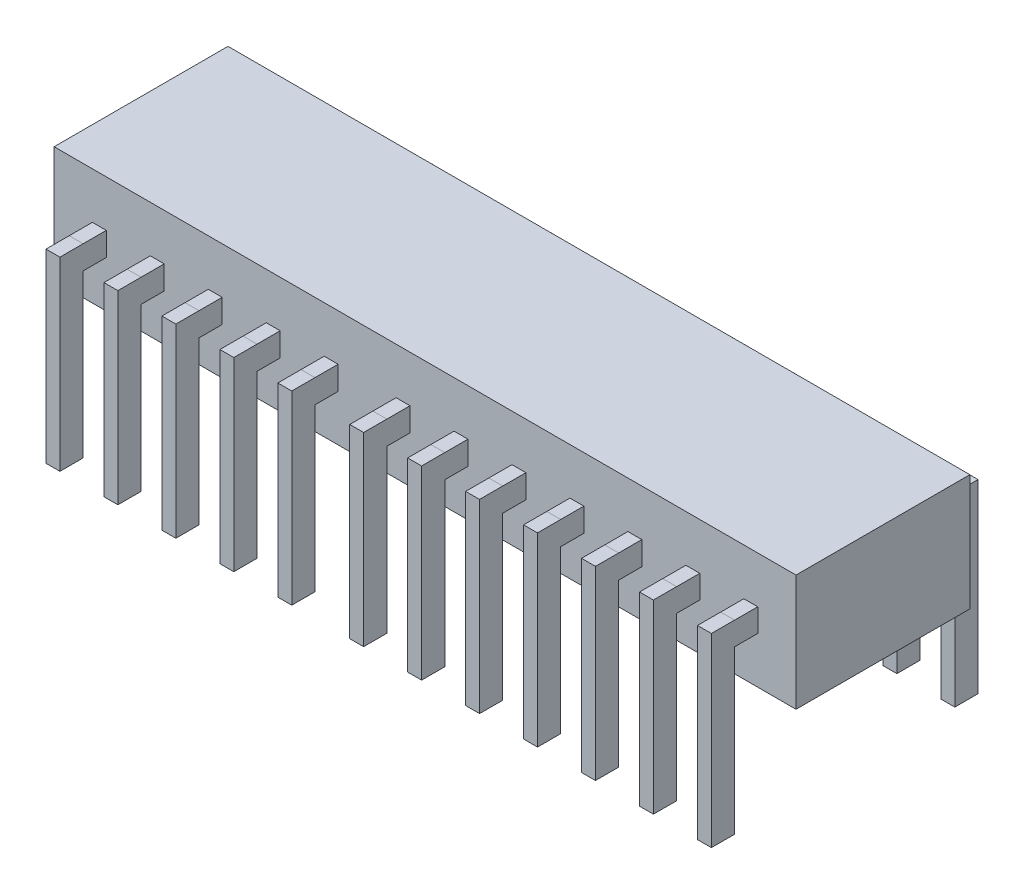
SolidWorks part; units mm, degrees
ref_plane "Front Plane" through (0, 0, 0) normal (0, 0, 1) x (1, 0, 0)
ref_plane "Top Plane" through (0, 0, 0) normal (0, 1, 0) x (1, 0, 0)
ref_plane "Right Plane" through (0, 0, 0) normal (1, 0, 0) x (0, 0, -1)
sketch "Sketch1" plane through (0, 0, 0) normal (0, 1, 0) x (1, 0, 0)
  line L0 (-13500, -3750) -> (18500.0025, -3750)
  line L1 (-13500, -3750) -> (-13500, 3750)
  line L2 (-13500, 3750) -> (18500.0025, 3750)
  line L3 (18500.0025, 3750) -> (18500.0025, -3750)
  line L4 (-11250, 5750) -> (-11850, 5750)
  line L5 (11850, -4750) -> (11850, -5750)
  line L6 (11850, -4750) -> (11250, -4750)
  line L7 (1250, -5750) -> (1250, -3750)
  line L8 (1250, -5750) -> (1850, -5750)
  line L9 (1850, -5750) -> (1850, -3750)
  line L10 (3750, -5750) -> (4350, -5750)
  line L11 (3750, -5750) -> (3750, -3750)
  line L12 (6250, -5750) -> (6850, -5750)
  line L13 (4350, -5750) -> (4350, -3750)
  line L14 (8750, -5750) -> (9350, -5750)
  line L15 (6250, -5750) -> (6250, -3750)
  line L16 (11250, -5750) -> (11850, -5750)
  line L17 (6850, -5750) -> (6850, -3750)
  line L18 (8750, -5750) -> (8750, -3750)
  line L19 (9350, -5750) -> (9350, -3750)
  line L20 (-11850, -5750) -> (-11850, -3750)
  line L21 (-11250, -5750) -> (-11250, -3750)
  line L22 (-9350, -5750) -> (-9350, -3750)
  line L23 (-8750, -5750) -> (-8750, -3750)
  line L24 (-6850, -5750) -> (-6850, -3750)
  line L25 (-11250, -5750) -> (-11850, -5750)
  line L26 (-6250, -5750) -> (-6250, -3750)
  line L27 (-8750, -5750) -> (-9350, -5750)
  line L28 (-4350, -5750) -> (-4350, -3750)
  line L29 (-6250, -5750) -> (-6850, -5750)
  line L30 (-3750, -5750) -> (-3750, -3750)
  line L31 (-3750, -5750) -> (-4350, -5750)
  line L32 (-1850, -5750) -> (-1850, -3750)
  line L33 (-1250, -5750) -> (-1850, -5750)
  line L34 (-1250, -5750) -> (-1250, -3750)
  line L35 (11250, -5750) -> (11250, -3750)
  line L36 (-1250, 5750) -> (-1250, 3750)
  line L37 (-1250, 5750) -> (-1850, 5750)
  line L38 (-1850, 5750) -> (-1850, 3750)
  line L39 (-3750, 5750) -> (-4350, 5750)
  line L40 (-3750, 5750) -> (-3750, 3750)
  line L41 (-6250, 5750) -> (-6850, 5750)
  line L42 (-4350, 5750) -> (-4350, 3750)
  line L43 (-8750, 5750) -> (-9350, 5750)
  line L44 (-6250, 5750) -> (-6250, 3750)
  line L45 (11850, -5750) -> (11850, -3750)
  line L46 (-6850, 5750) -> (-6850, 3750)
  line L47 (-8750, 5750) -> (-8750, 3750)
  line L48 (-9350, 5750) -> (-9350, 3750)
  line L49 (-11250, 5750) -> (-11250, 3750)
  line L50 (-11850, 5750) -> (-11850, 3750)
  line L51 (11850, 5750) -> (11850, 3750)
  line L52 (11250, 5750) -> (11250, 3750)
  line L53 (9350, 5750) -> (9350, 3750)
  line L54 (8750, 5750) -> (8750, 3750)
  line L55 (6850, 5750) -> (6850, 3750)
  line L56 (11250, 5750) -> (11850, 5750)
  line L57 (6250, 5750) -> (6250, 3750)
  line L58 (8750, 5750) -> (9350, 5750)
  line L59 (4350, 5750) -> (4350, 3750)
  line L60 (6250, 5750) -> (6850, 5750)
  line L61 (3750, 5750) -> (3750, 3750)
  line L62 (3750, 5750) -> (4350, 5750)
  line L63 (1850, 5750) -> (1850, 3750)
  line L64 (1250, 5750) -> (1850, 5750)
  line L65 (1250, 5750) -> (1250, 3750)
  line L66 (11250, -5750) -> (11250, -4750)
  line L67 (16850, -3750) -> (18500, -3750)
  line L68 (9350, -4750) -> (9350, -5750)
  line L69 (9350, -4750) -> (8750, -4750)
  line L70 (8750, -5750) -> (9350, -5750)
  line L71 (8750, -5750) -> (8750, -4750)
  line L72 (6850, -4750) -> (6850, -5750)
  line L73 (6850, -4750) -> (6250, -4750)
  line L74 (6250, -5750) -> (6850, -5750)
  line L75 (6250, -5750) -> (6250, -4750)
  line L76 (1850, -4750) -> (1850, -5750)
  line L77 (1850, -4750) -> (1250, -4750)
  line L78 (1250, -5750) -> (1850, -5750)
  line L79 (1250, -5750) -> (1250, -4750)
  line L80 (4350, -4750) -> (4350, -5750)
  line L81 (4350, -4750) -> (3750, -4750)
  line L82 (3750, -5750) -> (4350, -5750)
  line L83 (3750, -5750) -> (3750, -4750)
  line L84 (-1250, -4750) -> (-1250, -5750)
  line L85 (-1250, -4750) -> (-1850, -4750)
  line L86 (-11850, -5750) -> (-11250, -5750)
  line L87 (-9350, -5750) -> (-8750, -5750)
  line L88 (-6850, -5750) -> (-6250, -5750)
  line L89 (-4350, -5750) -> (-3750, -5750)
  line L90 (-1850, -5750) -> (-1250, -5750)
  line L91 (-1850, -5750) -> (-1850, -4750)
  line L92 (-3750, -4750) -> (-3750, -5750)
  line L93 (-3750, -4750) -> (-4350, -4750)
  line L94 (-4350, -5750) -> (-3750, -5750)
  line L95 (-4350, -5750) -> (-4350, -4750)
  line L96 (-6250, -4750) -> (-6250, -5750)
  line L97 (-6250, -4750) -> (-6850, -4750)
  line L98 (-6850, -5750) -> (-6250, -5750)
  line L99 (-6850, -5750) -> (-6850, -4750)
  line L100 (-11250, -4750) -> (-11250, -5750)
  line L101 (-11250, -4750) -> (-11850, -4750)
  line L102 (-11850, -5750) -> (-11250, -5750)
  line L103 (-11850, -5750) -> (-11850, -4750)
  line L104 (-8750, -4750) -> (-8750, -5750)
  line L105 (-8750, -4750) -> (-9350, -4750)
  line L106 (-9350, -5750) -> (-8750, -5750)
  line L107 (-9350, -5750) -> (-9350, -4750)
  line L108 (11850, 5750) -> (11850, 4750)
  line L109 (11850, 5750) -> (11250, 5750)
  line L110 (1250, 4750) -> (1850, 4750)
  line L111 (3750, 4750) -> (4350, 4750)
  line L112 (6250, 4750) -> (6850, 4750)
  line L113 (8750, 4750) -> (9350, 4750)
  line L114 (11250, 4750) -> (11850, 4750)
  line L115 (11250, 4750) -> (11250, 5750)
  line L116 (9350, 5750) -> (9350, 4750)
  line L117 (9350, 5750) -> (8750, 5750)
  line L118 (8750, 4750) -> (9350, 4750)
  line L119 (8750, 4750) -> (8750, 5750)
  line L120 (6850, 5750) -> (6850, 4750)
  line L121 (6850, 5750) -> (6250, 5750)
  line L122 (6250, 4750) -> (6850, 4750)
  line L123 (6250, 4750) -> (6250, 5750)
  line L124 (1850, 5750) -> (1850, 4750)
  line L125 (1850, 5750) -> (1250, 5750)
  line L126 (1250, 4750) -> (1850, 4750)
  line L127 (1250, 4750) -> (1250, 5750)
  line L128 (4350, 5750) -> (4350, 4750)
  line L129 (4350, 5750) -> (3750, 5750)
  line L130 (3750, 4750) -> (4350, 4750)
  line L131 (3750, 4750) -> (3750, 5750)
  line L132 (-1250, 5750) -> (-1250, 4750)
  line L133 (-1250, 5750) -> (-1850, 5750)
  line L134 (-11850, 4750) -> (-11250, 4750)
  line L135 (-9350, 4750) -> (-8750, 4750)
  line L136 (-6850, 4750) -> (-6250, 4750)
  line L137 (-4350, 4750) -> (-3750, 4750)
  line L138 (-1850, 4750) -> (-1250, 4750)
  line L139 (-1850, 4750) -> (-1850, 5750)
  line L140 (-3750, 5750) -> (-3750, 4750)
  line L141 (-3750, 5750) -> (-4350, 5750)
  line L142 (-4350, 4750) -> (-3750, 4750)
  line L143 (-4350, 4750) -> (-4350, 5750)
  line L144 (-6250, 5750) -> (-6250, 4750)
  line L145 (-6250, 5750) -> (-6850, 5750)
  line L146 (-6850, 4750) -> (-6250, 4750)
  line L147 (-6850, 4750) -> (-6850, 5750)
  line L148 (-11250, 5750) -> (-11250, 4750)
  line L149 (-11250, 5750) -> (-11850, 5750)
  line L150 (-11850, 4750) -> (-11250, 4750)
  line L151 (-11850, 4750) -> (-11850, 5750)
  line L152 (-8750, 5750) -> (-8750, 4750)
  line L153 (-8750, 5750) -> (-9350, 5750)
  line L154 (-9350, 4750) -> (-8750, 4750)
  line L155 (-9350, 4750) -> (-9350, 5750)
  line L156 (13750, -5750) -> (14350, -5750)
  line L157 (16250, -5750) -> (16850, -5750)
  line L158 (13750, -5750) -> (13750, -3750)
  line L159 (14350, -5750) -> (14350, -3750)
  line L160 (16250, -5750) -> (16250, -3750)
  line L161 (16850, -5750) -> (16850, -3750)
  line L162 (16850, -4750) -> (16850, -5750)
  line L163 (16850, -4750) -> (16250, -4750)
  line L164 (16250, -5750) -> (16850, -5750)
  line L165 (16250, -5750) -> (16250, -4750)
  line L166 (14350, -4750) -> (14350, -5750)
  line L167 (14350, -4750) -> (13750, -4750)
  line L168 (13750, -5750) -> (14350, -5750)
  line L169 (13750, -5750) -> (13750, -4750)
  line L171 (13750, 5750) -> (13750, 4750)
  line L172 (13750, 5750) -> (14350, 5750)
  line L173 (14350, 4750) -> (13750, 4750)
  line L174 (14350, 4750) -> (14350, 5750)
  line L175 (16250, 5750) -> (16250, 4750)
  line L176 (16250, 5750) -> (16850, 5750)
  line L177 (16850, 4750) -> (16250, 4750)
  line L178 (16850, 4750) -> (16850, 5750)
  line L179 (16850, 5750) -> (16850, 3750)
  line L180 (16250, 5750) -> (16250, 3750)
  line L181 (14350, 5750) -> (14350, 3750)
  line L182 (13750, 5750) -> (13750, 3750)
  line L183 (16250, 5750) -> (16850, 5750)
  line L184 (13750, 5750) -> (14350, 5750)
sketch "Sketch2" plane through (0, 0, 0) normal (0, 0, 1) x (1, 0, 0)
  line L0 (1250, 500) -> (1250, -7500)
  line L1 (-9350, 500) -> (-8750, 500)
  line L2 (1250, -7500) -> (1850, -7500)
  line L3 (1850, -7500) -> (1850, 500)
  line L4 (-11850.0182, 500) -> (-11250, 500)
  line L5 (3750, 500) -> (3750, -7500)
  line L6 (-6850, 500) -> (-6250, 500)
  line L7 (-4350, 500) -> (-3750, 500)
  line L8 (3750, -7500) -> (4350, -7500)
  line L9 (4350, -7500) -> (4350, 500)
  line L10 (-1850, 500) -> (-1250, 500)
  line L11 (6250, 500) -> (6250, -7500)
  line L12 (1250, 500) -> (1850, 500)
  line L13 (6250, -7500) -> (6850, -7500)
  line L14 (6850, -7500) -> (6850, 500)
  line L15 (8750, 500) -> (8750, -7500)
  line L16 (3750, 500) -> (4350, 500)
  line L17 (8750, -7500) -> (9350, -7500)
  line L18 (9350, -7500) -> (9350, 500)
  line L19 (11250, 500) -> (11250, -7500)
  line L20 (6250, 500) -> (6850, 500)
  line L21 (11250, -7500) -> (11850, -7500)
  line L22 (11850, -7500) -> (11850, 500)
  line L24 (-13553.4759, -2500) -> (13446.5241, -2500)
  line L25 (-11850.0182, -7500) -> (-11850.0182, 500)
  line L26 (-11250, -7500) -> (-11850.0182, -7500)
  line L27 (-11250, 500) -> (-11250, -7500)
  line L28 (-9350, -7500) -> (-9350, 500)
  line L29 (-8750, -7500) -> (-9350, -7500)
  line L30 (-8750, 500) -> (-8750, -7500)
  line L31 (-6850, -7500) -> (-6850, 500)
  line L32 (-6250, -7500) -> (-6850, -7500)
  line L33 (-6250, 500) -> (-6250, -7500)
  line L34 (-4350, -7500) -> (-4350, 500)
  line L35 (-3750, -7500) -> (-4350, -7500)
  line L36 (-3750, 500) -> (-3750, -7500)
  line L37 (-1850, -7500) -> (-1850, 500)
  line L38 (-1250, -7500) -> (-1850, -7500)
  line L39 (-1250, 500) -> (-1250, -7500)
  line L40 (13446.5241, -2500) -> (13446.5241, 2500)
  line L41 (8750, 500) -> (9350, 500)
  line L45 (13446.5241, 2500) -> (-13553.4759, 2500)
  line L46 (-13553.4759, 2500) -> (-13553.4759, -2500)
  line L47 (11250, 500) -> (11850, 500)
sketch "Sketch3" plane through (0, 0, 0) normal (1, 0, 0) x (0, 0, -1)
  line L1 (3750, 2500) -> (-3750, 2500)
  line L6 (3750, 500) -> (5750, 500)
  line L7 (5750, 500) -> (5750, -7500)
  line L8 (5750, -7500) -> (4750, -7500)
  line L9 (-3750, 2500) -> (-3750, -2500)
  line L10 (-3750, -2500) -> (3750, -2500)
  line L11 (3750, -2500) -> (3750, 2500)
  line L12 (4750, -7500) -> (4750, -500)
  line L13 (4750, -500) -> (3750, -500)
  line L15 (-4750, -500) -> (-3750, -500)
  line L16 (-4750, -7500) -> (-4750, -500)
  line L17 (-5750, -7500) -> (-4750, -7500)
  line L18 (-5750, 500) -> (-5750, -7500)
  line L19 (-3750, 500) -> (-5750, 500)
extrude "Boss-Extrude3" add sketch "Sketch1" along normal mid plane 5015 contours L3 L2 L1 L0 region at (2500.0013, 0, 0)
extrude "Boss-Extrude6" add sketch "Sketch1<14>" against normal blind 7494 and the other way blind 508 separate body contours L35 L16 L5 L6 | L19 L69 L18 L14 | L17 L73 L15 L12 | L13 L81 L11 L10 | L9 L77 L7 L8 | L34 L85 L32 L33 | L30 L93 L28 L31 | L26 L97 L24 L29 | L23 L105 L22 L27 | L21 L101 L20 L25 | L50 L134 L49 L4 | L48 L135 L47 L43 | L46 L136 L44 L41 | L42 L137 L40 L39 | L38 L138 L36 L37 | L65 L110 L63 L64 | L61 L111 L59 L62 | L57 L112 L55 L60 | L54 L113 L53 L58 | L52 L114 L51 L56 region at (-11550, 0, 5250) region at (-11550, 0, -5250) region at (-9050, 0, 5250) region at (-9050, 0, -5250) region at (-6550, 0, 5250) region at (-6550, 0, -5250) region at (-4050, 0, 5250) region at (-4050, 0, -5250) region at (-1550, 0, 5250) region at (-1550, 0, -5250) region at (1550, 0, 5250) region at (1550, 0, -5250) region at (4050, 0, 5250) region at (4050, 0, -5250) region at (6550, 0, 5250) region at (6550, 0, -5250) region at (9050, 0, 5250) region at (9050, 0, -5250) region at (11550, 0, 5250) region at (11550, 0, -5250)
sketch "Sketch1<14>" plane through (0, 0, 0) normal (0, 1, 0) x (1, 0, 0) same geometry as "Sketch1"
extrude "Boss-Extrude8" add sketch "Sketch1<17>" along normal mid plane 1015 contours L6 L45 L0 L35 | L69 L19 L0 L18 | L114 L52 L2 L51 | L113 L54 L2 L53 | L112 L57 L2 L55 | L73 L17 L0 L15 | L81 L13 L0 L11 | L77 L9 L0 L7 | L85 L34 L0 L32 | L138 L38 L2 L36 | L110 L65 L2 L63 | L111 L61 L2 L59 | L93 L30 L0 L28 | L97 L26 L0 L24 | L137 L42 L2 L40 | L136 L46 L2 L44 | L135 L48 L2 L47 | L105 L23 L0 L22 | L101 L21 L0 L20 | L134 L50 L2 L49 region at (-11550, 0, 4250) region at (-11550, 0, -4250) region at (-9050, 0, 4250) region at (-9050, 0, -4250) region at (-6550, 0, 4250) region at (-6550, 0, -4250) region at (-4050, 0, 4250) region at (-4050, 0, -4250) region at (-1550, 0, 4250) region at (-1550, 0, -4250) region at (1550, 0, 4250) region at (1550, 0, -4250) region at (4050, 0, 4250) region at (4050, 0, -4250) region at (6550, 0, 4250) region at (6550, 0, -4250) region at (9050, 0, 4250) region at (9050, 0, -4250) region at (11550, 0, 4250) region at (11550, 0, -4250)
sketch "Sketch1<17>" plane through (0, 0, 0) normal (0, 1, 0) x (1, 0, 0) same geometry as "Sketch1"
extrude "Boss-Extrude9" add sketch "Sketch1<18>" against normal blind 7501 and the other way blind 500 separate body contours L159 L167 L158 L156 | L161 L163 L160 L157 | L173 L174 L172 L171 | L177 L178 L176 L175 region at (14050, 0, 5250) region at (14050, 0, -5250) region at (16550, 0, 5250) region at (16550, 0, -5250)
sketch "Sketch1<18>" plane through (0, 0, 0) normal (0, 1, 0) x (1, 0, 0) same geometry as "Sketch1"
extrude "Boss-Extrude10" add sketch "Sketch1<19>" along normal mid plane 996 contours L173 L182 L2 L181 | L177 L180 L2 L179 | L167 L159 L0 L158 | L163 L161 L0 L160 region at (14050, 0, 4250) region at (14050, 0, -4250) region at (16550, 0, 4250) region at (16550, 0, -4250)
sketch "Sketch1<19>" plane through (0, 0, 0) normal (0, 1, 0) x (1, 0, 0) same geometry as "Sketch1"
